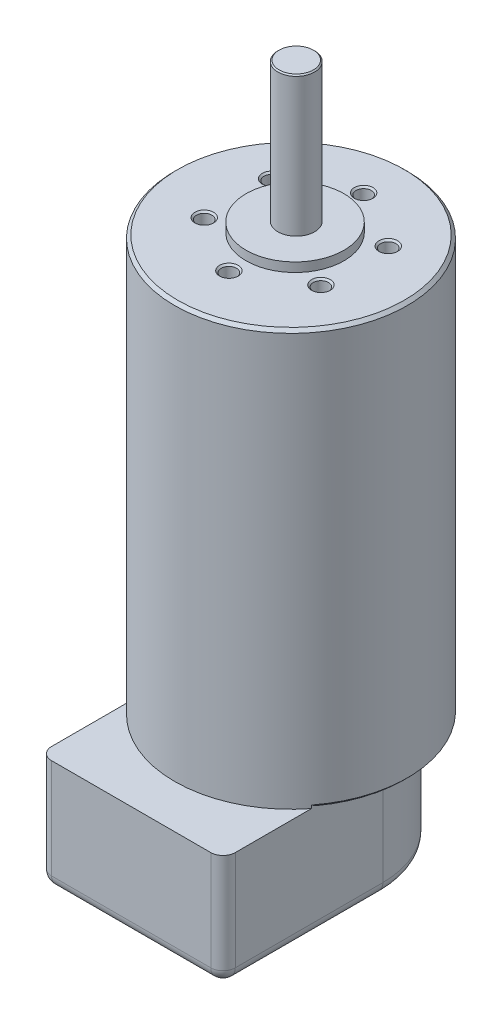
SolidWorks part; units mm, degrees
ref_plane "Front Plane" through (0, 0, 0) normal (0, 0, 1) x (1, 0, 0)
ref_plane "Top Plane" through (0, 0, 0) normal (0, 1, 0) x (1, 0, 0)
ref_plane "Right Plane" through (0, 0, 0) normal (1, 0, 0) x (0, 0, -1)
sketch "Sketch1" plane through (0, 0, 0) normal (0, 1, 0) x (1, 0, 0)
  line L2 (-15, 12.05) -> (-15, -12.05)
  line L3 (-13, -14.05) -> (13, -14.05)
  line L4 (15, 12.05) -> (15, -12.05)
  arc A0 (-15, 12.05) -> (15, 12.05) centre (0, 12.05) cw
  arc A1 (13, -14.05) -> (15, -12.05) centre (13, -12.05) ccw
  arc A2 (-15, -12.05) -> (-13, -14.05) centre (-13, -12.05) ccw
  point P0 (0, 27.05)
  point P3 (0, -14.05)
  point P4 (-15, 0)
  dimension "D3" = 2
  dimension "D1" = 41.1
  dimension "D2" = 30
extrude "Boss-Extrude1" add sketch "Sketch1" along normal blind 18.3
fillet "Fillet1" radius 2 6 edges at (-14.4142, 0, 13.4642) (-15, 0, 0) (0, 0, -27.05) (15, 0, 0) (14.4142, 0, 13.4642) (0, 0, 14.05)
sketch "Sketch2" plane through (0, 18.3, 0) normal (0, 1, 0) x (1, 0, 0)
  circle A0 centre (0, 12.05) radius 19
  arc A1 (15, 12.05) -> (-15, 12.05) centre (0, 12.05) ccw construction
  dimension "D1" = 38
extrude "Boss-Extrude2" add sketch "Sketch2" along normal blind 67.8 contours A0
chamfer "Chamfer1" distance 0.5 angle 45 1 edges at (0, 86.1, 6.95)
sketch "Sketch3" plane through (0, 86.1, 0) normal (0, 1, 0) x (1, 0, 0)
  circle A0 centre (0, 12.7086) radius 8
  dimension "D1" = 16
extrude "Boss-Extrude3" add sketch "Sketch3" along normal blind 1.5
sketch "Sketch4" plane through (0, 87.6, 0) normal (0, 1, 0) x (1, 0, 0)
  circle A0 centre (0, 12.9106) radius 3
  dimension "D1" = 6
extrude "Boss-Extrude4" add sketch "Sketch4" along normal blind 22.8
chamfer "Chamfer2" distance 0.2 angle 45 1 edges at (0, 110.4, -9.9106)
hole_wizard "M3x0.5 Tapped Hole1" positions "Sketch5" profile "Sketch6" tap size "M3x0.5" standard "ANSI Metric"
sketch "Sketch5" plane through (0, 86.1, 0) normal (0, 1, 0) x (1, 0, 0)
  circle A0 centre (0, 12.9106) radius 2.8 construction
  point P0 (0, 23.9106)
  dimension "D1" = 11
sketch "Sketch6" plane through (0, 86.1, -23.9106) normal (1, 0, 0) x (0, 0, 1)
  line L0 (0, 0) -> (0, 3.7511)
  line L1 (0, 3.7511) -> (1.25, 3)
  line L2 (1.25, 3) -> (1.25, 0.275)
  line L3 (1.25, 0.275) -> (1.525, 0)
  line L5 (1.525, 0) -> (0, 0)
  line L6 (-1.25, 0.275) -> (-1.525, 0) construction
  line L10 (0, 3.7511) -> (-1.25, 3) construction
  line L11 (0, -6.35) -> (0, 107.95) construction
  dimension "Tap Drill Dia." = 2.5
  dimension "Tap Drill Depth" = 3
  dimension "Near C'Sink Dia." = 3.05
  dimension "Near C'Sink Angle" = 90
  dimension "Drill Angle" = 118
cosmetic thread "Hole Thread1" parameters "D1"=3, "D2"=3
ref_axis "Axis1" through (0, 110.2, -12.9106) along (0, -1, 0)
pattern_circular "CirPattern1" count 6 every 60 about axis through (0, 110.2, -12.9106) along (0, -1, 0) of "M3x0.5 Tapped Hole1"
chamfer "Chamfer3" distance 0.5 angle 45 1 edges at (0, 18.3, -31.05)
